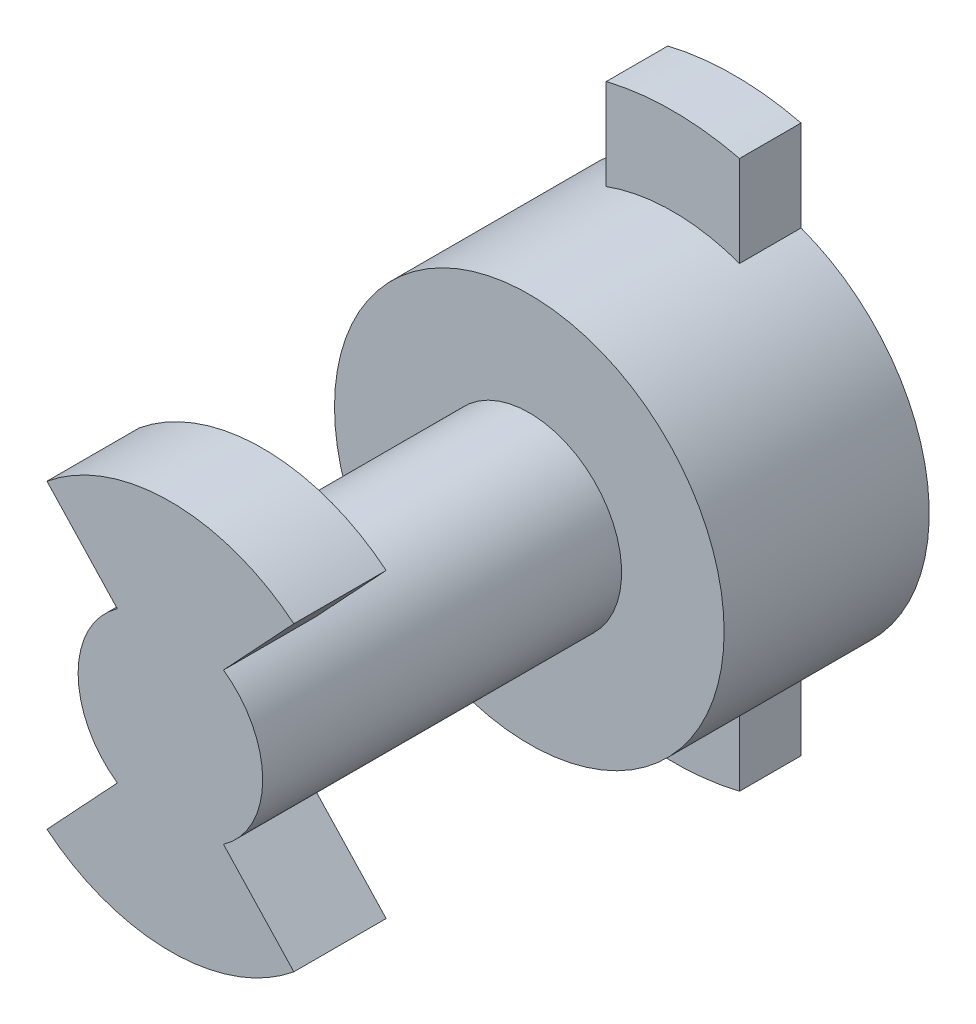
SolidWorks part; units mm, degrees
ref_plane "Front Plane" through (0, 0, 0) normal (0, 0, 1) x (1, 0, 0)
ref_plane "Top Plane" through (0, 0, 0) normal (0, 1, 0) x (1, 0, 0)
ref_plane "Right Plane" through (0, 0, 0) normal (1, 0, 0) x (0, 0, -1)
sketch "Sketch1" plane through (0, 0, 0) normal (0, 0, 1) x (1, 0, 0)
  line L2 (6.0193, 7.3497) -> (2.5898, 3.6801)
  line L3 (-2.5898, 3.6801) -> (-6.0193, 7.3497)
  line L4 (2.5898, -3.6801) -> (6.0193, -7.3497)
  line L5 (-2.5898, -3.6801) -> (-6.0193, -7.3497)
  arc A0 (6.0193, 7.3497) -> (-6.0193, 7.3497) centre (0, 0) ccw
  circle A1 centre (0, 0) radius 4.5
  arc A2 (-6.0193, -7.3497) -> (6.0193, -7.3497) centre (0, 0) ccw
  point P7 (0, 0)
  point P10 (0, 0)
extrude "Boss-Extrude1" add sketch "Sketch1" along normal blind 4.5 contours A1 L2 A0 L3 | A1 | L5 A2 L4 A1 region at (0, 6.8054, 0) region at (0, 0, 0) region at (0, -6.8054, 0)
extrude "Boss-Extrude2" add sketch "Sketch1<3>" against normal blind 23 contours A1 region at (0, 0, 0)
sketch "Sketch1<3>" plane through (0, 0, 0) normal (0, 0, 1) x (1, 0, 0) same geometry as "Sketch1"
ref_plane "Plane1" through (0, 0, -23) normal (0, 0, -1) x (-1, 0, 0)
sketch "Sketch2" plane through (0, 0, -23) normal (0, 0, -1) x (-1, 0, 0)
  line L1 (-3.25, -8.9256) -> (-3.25, -13.3604)
  line L2 (3.25, -8.9256) -> (3.25, -13.3604)
  line L3 (3.25, 13.3604) -> (3.25, 8.9256)
  line L4 (-3.25, 13.3604) -> (-3.25, 8.9256)
  circle A0 centre (0, 0) radius 9.4989
  arc A1 (3.25, 13.3604) -> (-3.25, 13.3604) centre (0, 0) ccw
  arc A2 (-3.25, -13.3604) -> (3.25, -13.3604) centre (0, 0) ccw
  dimension "D1" = 27.5
extrude "Boss-Extrude3" add sketch "Sketch2" against normal blind 10 contours A0 region at (0, 0, -23)
extrude "Boss-Extrude4" add sketch "Sketch2<3>" against normal blind 3 contours L3 A1 L4 A0 | L1 A2 L2 A0 region at (0, -11.4637, -23) region at (0, 11.4637, -23)
sketch "Sketch2<3>" plane through (0, 0, -23) normal (0, 0, -1) x (-1, 0, 0) same geometry as "Sketch2"
